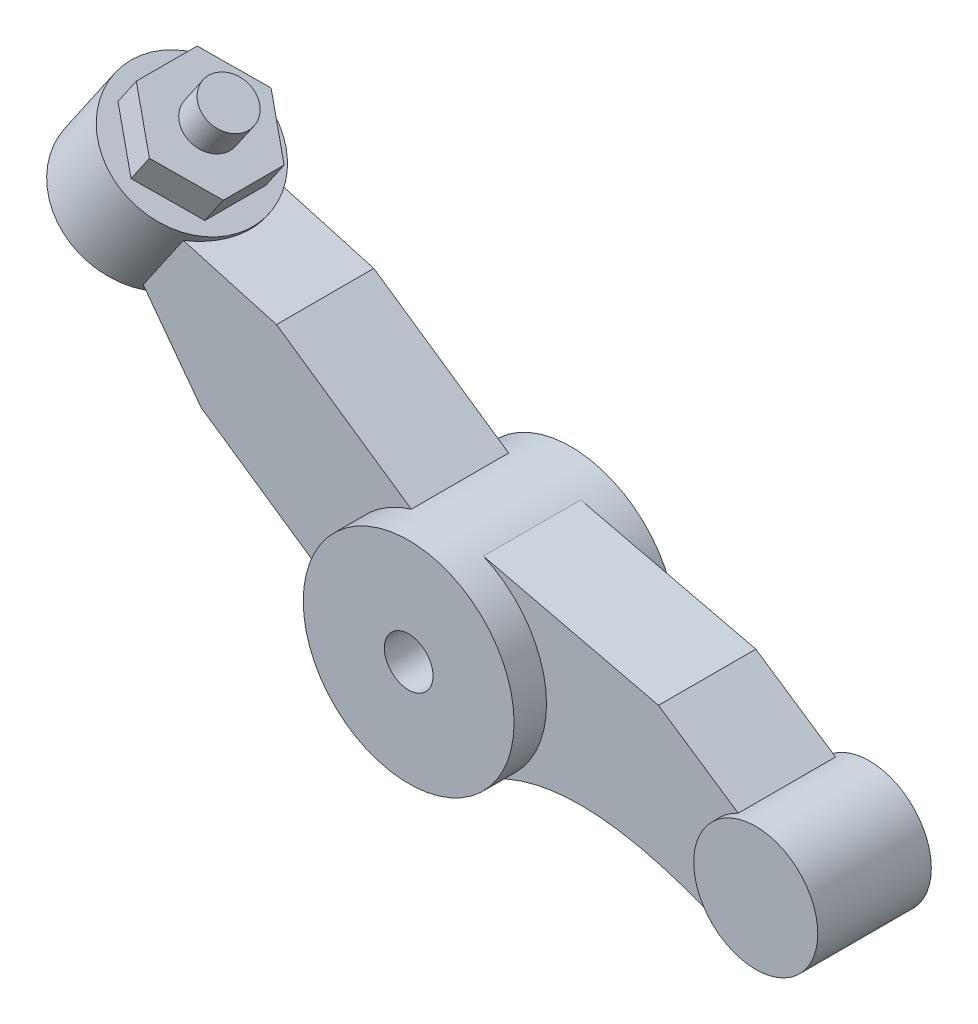
SolidWorks part; units mm, degrees
ref_plane "Front Plane" through (0, 0, 0) normal (0, 0, 1) x (1, 0, 0)
ref_plane "Top Plane" through (0, 0, 0) normal (0, 1, 0) x (1, 0, 0)
ref_plane "Right Plane" through (0, 0, 0) normal (1, 0, 0) x (0, 0, -1)
sketch "Sketch1" plane through (0, 0, 0) normal (0, 0, 1) x (1, 0, 0)
  line L0 (-2.832, 0) -> (4.0762, 0) construction
  line L1 (0, 2.2443) -> (0, 0) construction
  line L2 (0, 0) -> (-3.6604, 2.5129) construction
  line L3 (3.6635, 0.0165) -> (2.6808, 0.6771)
  line L4 (2.6808, 0.6771) -> (0.5216, 1.1908)
  line L5 (-3.8529, 2.2326) -> (-3.468, 2.7932)
  line L6 (-3.468, 2.7932) -> (-2.0298, 2.3881)
  line L7 (-2.0298, 2.3881) -> (-0.3675, 1.247)
  line L8 (-3.8529, 2.2326) -> (-2.958, 1.036)
  line L9 (-2.958, 1.036) -> (-1.2957, -0.1051)
  circle A0 centre (0, 0) radius 1.3
  circle A1 centre (0, 0) radius 0.3
  circle A2 centre (3.98, -0.68) radius 0.765
  spline S0 degree 3 poles (3.6635, -1.3765) (2.7563, -0.9673) (1.6218, -0.6145) (0.6766, -1.11) knots 0 0 0 0 1 1 1 1
  dimension "D1" = 0.6
  dimension "D2" = 2.6
  dimension "D3" = 1.53
  dimension "D4" = 0.68
  dimension "D5" = 3.98
  dimension "D6" = 4.44
  dimension "D7" = 0.68
  dimension "D8" = 0.82
  dimension "D9" = 34.47
extrude "Boss-Extrude1" add sketch "Sketch1" along normal mid plane 2 contours A0 A1 region at (1.0574, 0.6912, 0)
extrude "Boss-Extrude2" add sketch "Sketch1<3>" along normal mid plane 1.4 separate body contours A2 region at (3.98, -0.68, 0)
sketch "Sketch1<3>" plane through (0, 0, 0) normal (0, 0, 1) x (1, 0, 0) same geometry as "Sketch1"
extrude "Boss-Extrude3" add sketch "Sketch1<4>" along normal mid plane 1.2 contours S0 A2 L3 L4 A0 region at (2.1957, -0.0839, 0)
sketch "Sketch1<4>" plane through (0, 0, 0) normal (0, 0, 1) x (1, 0, 0) same geometry as "Sketch1"
extrude "Boss-Extrude4" add sketch "Sketch1<5>" along normal mid plane 1.2 contours A0 L7 L6 L5 L8 L9 region at (-2.1883, 1.5023, 0)
sketch "Sketch1<5>" plane through (0, 0, 0) normal (0, 0, 1) x (1, 0, 0) same geometry as "Sketch1"
sketch "Sketch2" plane through (0, 0, 0) normal (0, 0, 1) x (1, 0, 0)
  line L0 (-3.8529, 2.2326) -> (-3.4454, 2.8262)
  line L1 (-3.4454, 2.8262) -> (-3.7751, 3.0526)
  line L2 (-3.7751, 3.0526) -> (-4.8152, 1.5377)
  line L3 (-3.8529, 2.2326) -> (-4.308, 1.9905)
  line L4 (-3.8529, 2.2326) -> (-3.468, 2.7932) construction
  arc A0 (-4.308, 1.9905) -> (-4.8152, 1.5377) centre (-4.6171, 1.8262) cw
  dimension "D3" = 0.35
  dimension "D1" = 0.72
  dimension "D2" = 0.4
  dimension "D4" = 1
revolve "Revolve1" add sketch "Sketch2" angle 360 about L2
sketch "Sketch3" plane through (0, 0, 0) normal (0, 0, 1) x (1, 0, 0)
  line L0 (-3.6733, 3.201) -> (-4.2845, 2.3106)
  line L1 (-4.2845, 2.3106) -> (-5.0347, 2.8257)
  line L2 (-5.0347, 2.8257) -> (-4.4235, 3.716)
  line L3 (-4.4235, 3.716) -> (-3.6733, 3.201)
  line L5 (-4.1826, 2.459) -> (-3.7751, 3.0526) construction
  line L8 (-3.4454, 2.8262) -> (-4.1049, 3.279) construction
  line L9 (-4.5124, 2.6854) -> (-3.8529, 2.2326) construction
  dimension "D1" = 1.08
  dimension "D2" = 0.91
  dimension "D3" = 0.18
revolve "Revolve2" add sketch "Sketch3" angle 360 about L0
sketch "Sketch4" plane through (0.3169, 0.4617, 0) normal (0.566, 0.8244, 0) x (0.8244, -0.566, 0)
  line L1 (-4.84, 0.7506) -> (-5.49, 0.3753)
  line L2 (-5.49, 0.3753) -> (-5.49, -0.3753)
  line L3 (-5.49, -0.3753) -> (-4.84, -0.7506)
  line L4 (-4.84, -0.7506) -> (-4.19, -0.3753)
  line L5 (-4.19, -0.3753) -> (-4.19, 0.3753)
  line L6 (-4.19, 0.3753) -> (-4.84, 0.7506)
  circle A0 centre (-4.84, 0) radius 0.65 construction
  dimension "D1" = 1.3
extrude "Boss-Extrude5" add sketch "Sketch4" along normal blind 0.4
sketch "Sketch5" plane through (0.5433, 0.7914, 0) normal (0.566, 0.8244, 0) x (0.8244, -0.566, 0)
  circle A0 centre (-4.84, 0) radius 0.3
  dimension "D1" = 0.6
extrude "Boss-Extrude6" add sketch "Sketch5" along normal blind 0.4
